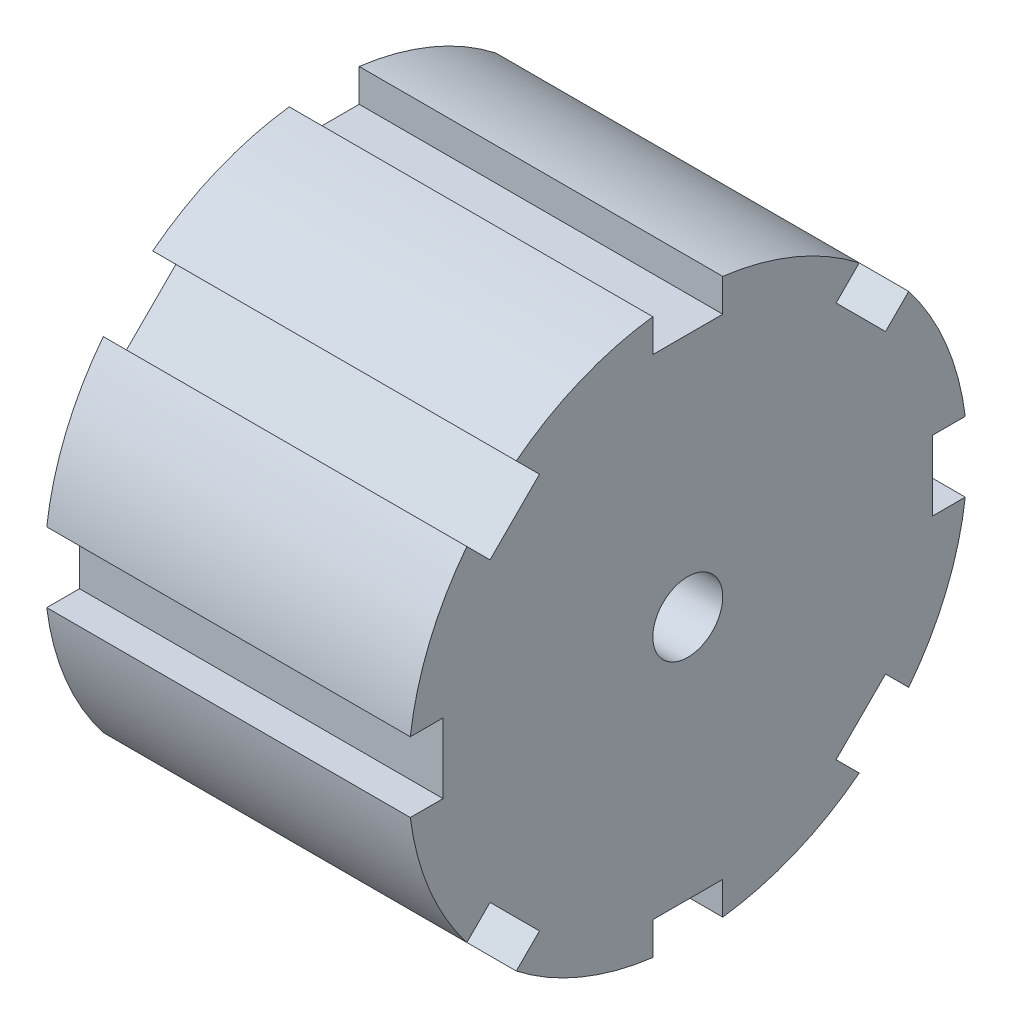
SolidWorks part; units mm, degrees
ref_plane "Front Plane" through (0, 0, 0) normal (0, 0, 1) x (1, 0, 0)
ref_plane "Top Plane" through (0, 0, 0) normal (0, 1, 0) x (1, 0, 0)
ref_plane "Right Plane" through (0, 0, 0) normal (1, 0, 0) x (0, 0, -1)
sketch "Sketch1" plane through (0, 0, 0) normal (1, 0, 0) x (0, 0, -1)
  circle A0 centre (0, 0) radius 25.4
  dimension "D1" = 50.8
extrude "Boss-Extrude1" add sketch "Sketch1" against normal blind 33.02 contours A0
sketch "Sketch2" plane through (0, 0, 0) normal (1, 0, 0) x (0, 0, -1)
  line L0 (22.4506, 17.9605) -> (17.9605, 22.4506)
  line L1 (3.175, 22.225) -> (-3.175, 22.225)
  line L2 (3.175, 22.225) -> (3.175, 28.575)
  line L3 (3.175, 28.575) -> (-3.175, 28.575)
  line L4 (-3.175, 22.225) -> (-3.175, 28.575)
  line L5 (3.175, 22.225) -> (-3.175, 28.575) construction
  line L6 (3.175, 28.575) -> (-3.175, 22.225) construction
  line L7 (13.4704, 17.9605) -> (17.9605, 22.4506)
  line L8 (17.9605, 13.4704) -> (22.4506, 17.9605)
  line L9 (17.9605, 13.4704) -> (13.4704, 17.9605)
  line L10 (28.575, -3.175) -> (28.575, 3.175)
  line L11 (22.225, 3.175) -> (28.575, 3.175)
  line L12 (22.225, -3.175) -> (28.575, -3.175)
  line L13 (22.225, -3.175) -> (22.225, 3.175)
  line L14 (17.9605, -22.4506) -> (22.4506, -17.9605)
  line L15 (17.9605, -13.4704) -> (22.4506, -17.9605)
  line L16 (13.4704, -17.9605) -> (17.9605, -22.4506)
  line L17 (13.4704, -17.9605) -> (17.9605, -13.4704)
  line L18 (-3.175, -28.575) -> (3.175, -28.575)
  line L19 (3.175, -22.225) -> (3.175, -28.575)
  line L20 (-3.175, -22.225) -> (-3.175, -28.575)
  line L21 (-3.175, -22.225) -> (3.175, -22.225)
  line L22 (-22.4506, -17.9605) -> (-17.9605, -22.4506)
  line L23 (-13.4704, -17.9605) -> (-17.9605, -22.4506)
  line L24 (-17.9605, -13.4704) -> (-22.4506, -17.9605)
  line L25 (-17.9605, -13.4704) -> (-13.4704, -17.9605)
  line L26 (-28.575, 3.175) -> (-28.575, -3.175)
  line L27 (-22.225, -3.175) -> (-28.575, -3.175)
  line L28 (-22.225, 3.175) -> (-28.575, 3.175)
  line L29 (-22.225, 3.175) -> (-22.225, -3.175)
  line L30 (-17.9605, 22.4506) -> (-22.4506, 17.9605)
  line L31 (-17.9605, 13.4704) -> (-22.4506, 17.9605)
  line L32 (-13.4704, 17.9605) -> (-17.9605, 22.4506)
  line L33 (-13.4704, 17.9605) -> (-17.9605, 13.4704)
  circle A0 centre (0, 0) radius 25.4 construction
  circle A1 centre (0, 0) radius 3.175
  point P0 (0, 25.4)
  point P38 (0, 0)
  dimension "D4" = 6.35
  dimension "D1" = 6.35
  dimension "D2" = 6.35
  dimension "D3" = 8
extrude "Cut-Extrude1" cut sketch "Sketch2" against normal blind 109.22
